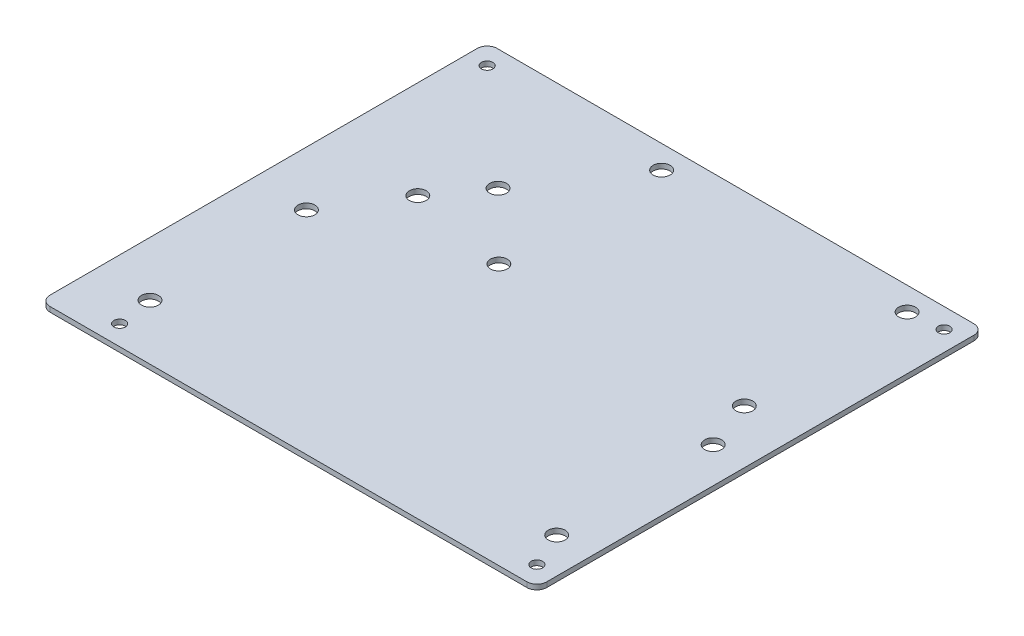
SolidWorks part; units mm, degrees
ref_plane "Front Plane" through (0, 0, 0) normal (0, 0, 1) x (1, 0, 0)
ref_plane "Top Plane" through (0, 0, 0) normal (0, 1, 0) x (1, 0, 0)
ref_plane "Right Plane" through (0, 0, 0) normal (1, 0, 0) x (0, 0, -1)
sketch "Sketch1" plane through (0, 0, 0) normal (0, 1, 0) x (1, 0, 0)
  line L1 (0, 0) -> (158.75, 0)
  line L2 (0, 0) -> (0, 142.875)
  line L4 (158.75, 0) -> (158.75, 142.875)
  line L19 (158.75, 142.875) -> (0, 142.875)
  line L21 (351.9786, 184.7613) -> (351.9786, -3.4747) construction
  dimension "D1" = 142.875
  dimension "D2" = 351.9786
  dimension "D5" = 158.75
extrude "Boss-Extrude1" add sketch "Sketch1" along normal blind 1.6002 contours L1 L19 L4 L2 region at (79.375, 0, -71.4375)
fillet "Fillet1" radius 3.175 4 edges at (158.75, 0.8001, 0) (0, 0.8001, -142.875) (158.75, 0.8001, -142.875) (0, 0.8001, 0)
sketch "Sketch2" plane through (0, 1.6002, 0) normal (0, 1, 0) x (1, 0, 0)
  line L0 (3.175, 139.7) -> (155.575, 3.175) construction
  line L1 (0, 3.175) -> (0, 139.7) construction
  line L2 (152.4, 136.525) -> (6.35, 136.525) construction
  line L3 (152.4, 136.525) -> (152.4, 6.35) construction
  line L4 (152.4, 6.35) -> (6.35, 6.35) construction
  line L5 (6.35, 136.525) -> (6.35, 6.35) construction
  line L6 (152.4, 136.525) -> (6.35, 6.35) construction
  line L7 (152.4, 6.35) -> (6.35, 136.525) construction
  line L8 (155.575, 142.875) -> (3.175, 142.875) construction
  circle A0 centre (6.35, 136.525) radius 1.8288
  circle A1 centre (152.4, 136.525) radius 1.8288
  circle A2 centre (152.4, 6.35) radius 1.8288
  circle A4 centre (19.05, 6.35) radius 1.8288
  point P2 (79.375, 71.4375)
  dimension "D3" = 3.6576
  dimension "D4" = 19.05
  dimension "D1" = 6.35
  dimension "D2" = 6.35
extrude "Cut-Extrude1" cut sketch "Sketch2" against normal through all
sketch "Sketch5" plane through (0, 1.6002, 0) normal (0, 1, 0) x (1, 0, 0)
  circle A0 centre (63.1631, 135.4715) radius 2.7051
  circle A1 centre (141.663, 135.4288) radius 2.7051
  circle A2 centre (63.1348, 83.4715) radius 2.7051
  circle A3 centre (141.6347, 83.4288) radius 2.7051
  circle A4 centre (17.4, 67.7) radius 2.7051
  circle A5 centre (147.382, 67.721) radius 2.7051
  circle A6 centre (147.4, 17.7) radius 2.7051
  circle A7 centre (17.4, 17.7) radius 2.7051
  circle A8 centre (42.0343, 104.323) radius 2.7051
  circle A10 centre (31.2393, 89.464) radius 2.7051
  dimension "D1" = 5.4102
extrude "Cut-Extrude2" cut sketch "Sketch5" against normal through all
